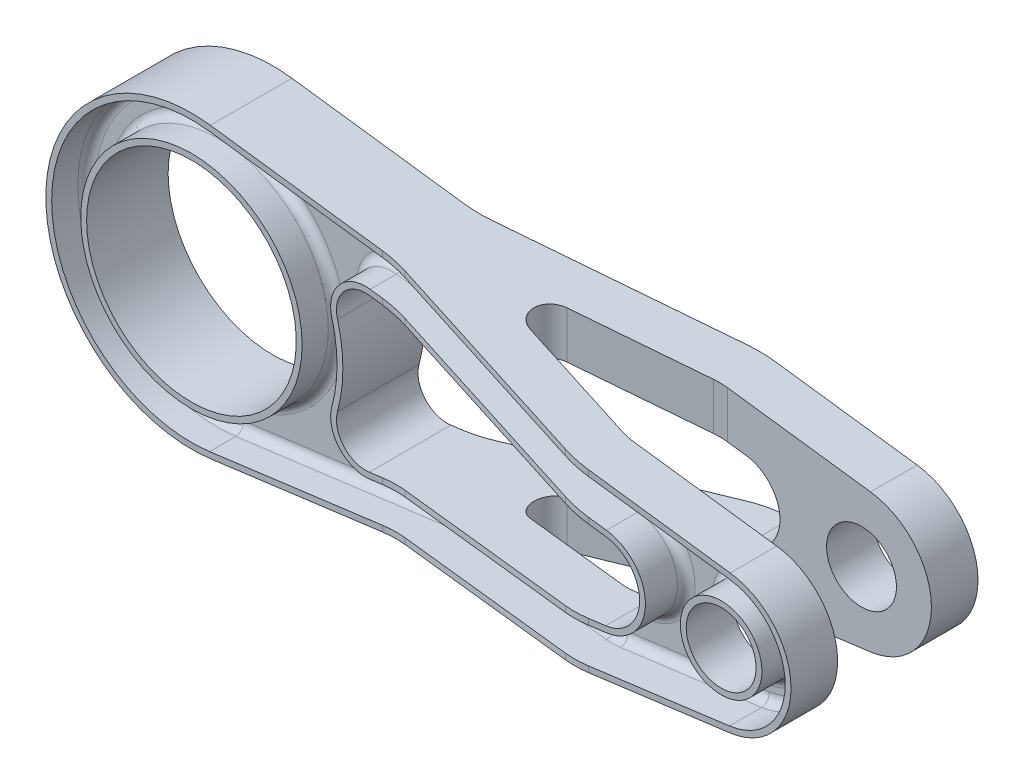
SolidWorks part; units mm, degrees
material "Molybdenum"
ref_plane "Front Plane" through (0, 0, 0) normal (0, 0, 1) x (1, 0, 0)
ref_plane "Top Plane" through (0, 0, 0) normal (0, 1, 0) x (1, 0, 0)
ref_plane "Right Plane" through (0, 0, 0) normal (1, 0, 0) x (0, 0, -1)
sketch "Sketch1" plane through (0, 0, 0) normal (0, 0, 1) x (1, 0, 0)
  line L0 (3.25, 24.7878) -> (101.56, 11.8982)
  line L1 (101.56, -11.8982) -> (3.25, -24.7878)
  line L2 (100, 0) -> (112, 0) construction
  line L3 (30.5507, 13.1399) -> (80.18, 6.6329)
  line L6 (80.18, -6.6329) -> (30.5507, -13.1399)
  circle A0 centre (0, 0) radius 18
  circle A1 centre (100, 0) radius 6
  arc A2 (101.56, -11.8982) -> (101.56, 11.8982) centre (100, 0) ccw
  arc A3 (3.25, 24.7878) -> (3.25, -24.7878) centre (0, 0) ccw
  arc A4 (80.18, -6.6329) -> (80.18, 6.6329) centre (79.3103, 0) ccw
  arc A7 (30.5507, -13.1399) -> (25.078, -6.8626) centre (29.9007, -8.1824) cw
  arc A8 (25.078, 6.8626) -> (30.5507, 13.1399) centre (29.9007, 8.1824) cw
  arc A9 (25.078, -6.8626) -> (25.078, 6.8626) centre (0, 0) ccw
  point P14 (21.7154, -14.2983)
  dimension "D1" = 25
  dimension "D2" = 36
  dimension "D3" = 12
  dimension "D4" = 12
  dimension "D6" = 8
  dimension "D7" = 5
  dimension "D10" = 8
  dimension "D5" = 100
  dimension "D8" = 8
  dimension "D9" = 8
extrude "1" add sketch "Sketch1" along normal blind 30
sketch "Sketch2" plane through (0, 0, 0) normal (0, 1, 0) x (1, 0, 0)
  line L0 (37.1794, 7.4932) -> (72.8206, 15.5579)
  line L1 (-25, 7) -> (32.7655, 7)
  line L2 (75.8938, 8.0511) -> (120, 8.0511) construction
  line L3 (54.322, 3.1699) -> (74.8041, 7.8045)
  line L4 (77.0111, 8.0511) -> (112, 8.0511)
  line L5 (77.2345, 16.0511) -> (112, 16.0511)
  line L6 (112, 16.0511) -> (112, 8.0511)
  line L7 (112, 16.0511) -> (112, 30.5161) construction
  line L8 (0, 0) -> (120.2315, 0) construction
  line L9 (112, -16.0511) -> (112, -8.0511)
  line L10 (-25, -1) -> (35.8938, -1) construction
  line L11 (120, 8.0511) -> (120, 30.5161) construction
  line L12 (77.2345, -16.0511) -> (112, -16.0511)
  line L13 (35, 7) -> (75, 16.0511) construction
  line L14 (75, 16.0511) -> (112, 16.0511) construction
  line L15 (-25, 7) -> (35, 7) construction
  line L16 (35.8938, -1) -> (75.8938, 8.0511) construction
  line L17 (77.0111, -8.0511) -> (112, -8.0511)
  line L18 (54.322, -3.1699) -> (74.8041, -7.8045)
  line L19 (-25, -7) -> (32.7655, -7)
  line L20 (37.1794, -7.4932) -> (72.8206, -15.5579)
  line L21 (-25, 0) -> (-25, -30) construction
  line L30 (-25, 7) -> (-25, -7)
  arc A0 (72.8206, 15.5579) -> (77.2345, 16.0511) centre (77.2345, -3.9489) cw
  arc A1 (32.7655, 7) -> (37.1794, 7.4932) centre (32.7655, 27) ccw
  arc A2 (74.8041, 7.8045) -> (77.0111, 8.0511) centre (77.0111, -1.9489) cw
  arc A3 (74.8041, -7.8045) -> (77.0111, -8.0511) centre (77.0111, 1.9489) ccw
  arc A4 (32.7655, -7) -> (37.1794, -7.4932) centre (32.7655, -27) cw
  arc A5 (72.8206, -15.5579) -> (77.2345, -16.0511) centre (77.2345, 3.9489) ccw
  arc A6 (54.322, -3.1699) -> (54.322, 3.1699) centre (55.0392, 0) cw
  point P19 (75, 16.0511)
  point P38 (35, -7)
  point P39 (35, 7)
  point P41 (75, -16.0511)
  dimension "D2" = 75
  dimension "D3" = 10
  dimension "D4" = 20
  dimension "D8" = 14
  dimension "D5" = 3.25
  dimension "D1" = 8
  dimension "D6" = 12.75
  dimension "D7" = 35
extrude "2" add sketch "Sketch2" along normal mid plane 50 separate body
combine bodies "3" operation type common bodies to combine 102 101
shell "4" thickness 1 removed face at (34.9793, -16.5935, 7.1851) removed face at (34.9793, 16.5935, 7.1851) removed face at (75.0207, -11.3436, 15.866) removed face at (75.0207, 11.3436, 15.866) removed face at (94, 0, 16.0511) removed face at (21.8126, 0, 7) removed face at (55, -13.9685, 11.5255) removed face at (55, 13.9685, 11.5255)
fillet "5" radius 1.5 30 edges at (50.9085, -14.505, 1) (50.9085, 14.505, 1) (52.0566, 11.3288, 3.0276) (64.3423, 9.718, 6.4625) (75.7897, 8.2171, 8.9831) (78.6605, 7.8407, 9.0511) (87, 0, 9.0511) (78.6605, -7.8407, 9.0511) (75.7897, -8.2171, 8.9831) (64.3423, -9.718, 6.4625) (40.7946, 12.8054, 1) (25.3781, 12.1252, 1) (25, 0, 1) (25.3781, -12.1252, 1) (52.0566, -17.3801, 3.0276) (64.3423, -15.7693, 6.4625) (75.7897, -14.2684, 8.9831) (89.2205, -12.5075, 9.0511) (111, 0, 9.0511) (89.2205, 12.5075, 9.0511) (75.7897, 14.2684, 8.9831) (64.3423, 15.7693, 6.4625) (27.0143, -20.6635, 1) (-24, 0, 1) (107, 0, 9.0511) (19, 0, 1) (52.0566, -11.3288, 3.0276) (40.7946, -12.8054, 1) (52.0566, 17.3801, 3.0276) (27.0143, 20.6635, 1)
mirror "6" about plane through (0, 0, 0) normal (0, 0, 1) of bodies 103
